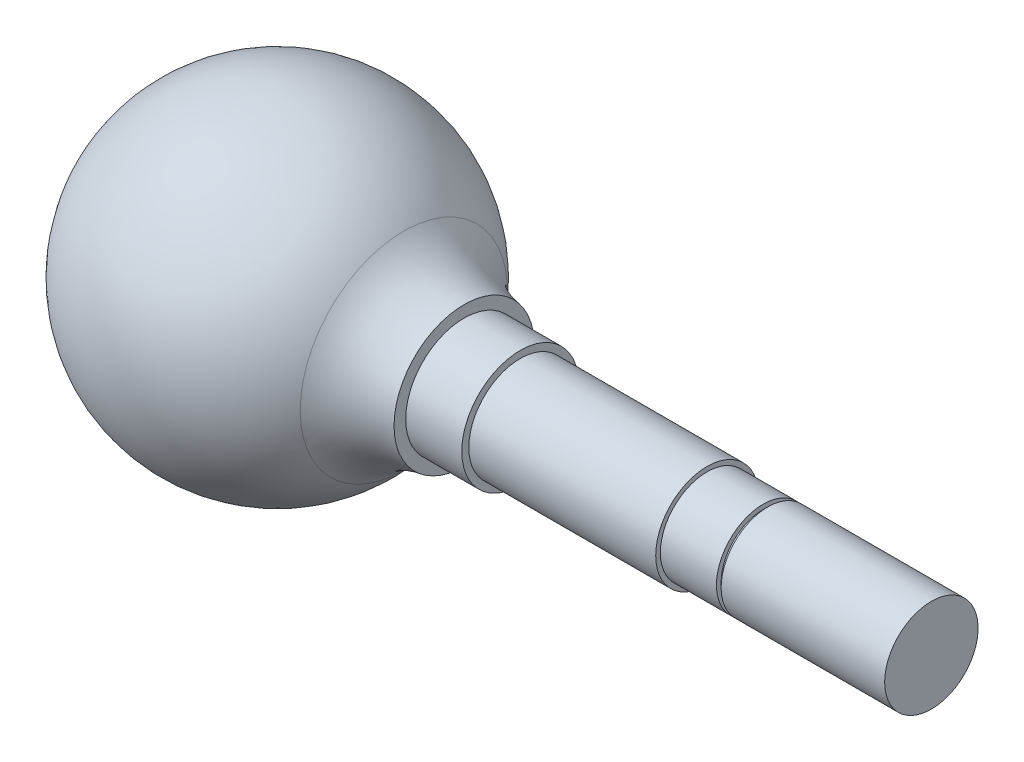
SolidWorks part; units mm, degrees
ref_plane "前视基准面" through (0, 0, 0) normal (0, 0, 1) x (1, 0, 0)
ref_plane "上视基准面" through (0, 0, 0) normal (0, 1, 0) x (1, 0, 0)
ref_plane "右视基准面" through (0, 0, 0) normal (1, 0, 0) x (0, 0, -1)
sketch "Sketch1" plane through (0, 0, 0) normal (0, 0, 1) x (1, 0, 0)
  line L0 (0, 35) -> (0, -35)
  arc A0 (0, 35) -> (0, -35) centre (0, 0) ccw
  dimension "D1" = 70
revolve "Revolve1" add sketch "Sketch1" angle 360 about L0
sketch "Sketch2" plane through (0, 0, 0) normal (0, 0, 1) x (1, 0, 0)
  line L0 (0, 0) -> (35, 0) construction
  line L1 (52, 11) -> (92, 11)
  line L2 (35, 0) -> (140, 0)
  line L4 (92, 11) -> (92, 10)
  line L5 (92, 10) -> (104, 10)
  line L6 (104, 10) -> (104, 9)
  line L7 (104, 9) -> (105, 9)
  line L8 (105, 9) -> (105, 10)
  line L9 (105, 10) -> (140, 10)
  line L10 (140, 10) -> (140, 0)
  line L11 (52, 11) -> (52, 12.5)
  line L12 (52, 12.5) -> (40, 12.5)
  line L13 (40, 12.5) -> (40, 15)
  line L14 (40, 15) -> (31.6228, 15)
  circle A0 centre (0, 0) radius 35 construction
  arc A2 (31.6228, 15) -> (35, 0) centre (0, 0) cw
  dimension "D2" = 25
  dimension "D9" = 140
  dimension "D1" = 22
  dimension "D3" = 1
  dimension "D4" = 12
  dimension "D5" = 92
  dimension "D6" = 20
  dimension "D7" = 12
  dimension "D8" = 30
revolve "Revolve2" add sketch "Sketch2" angle 360 about L0
fillet "Fillet1" radius 20 1 edges at (31.6228, 0, 15)
